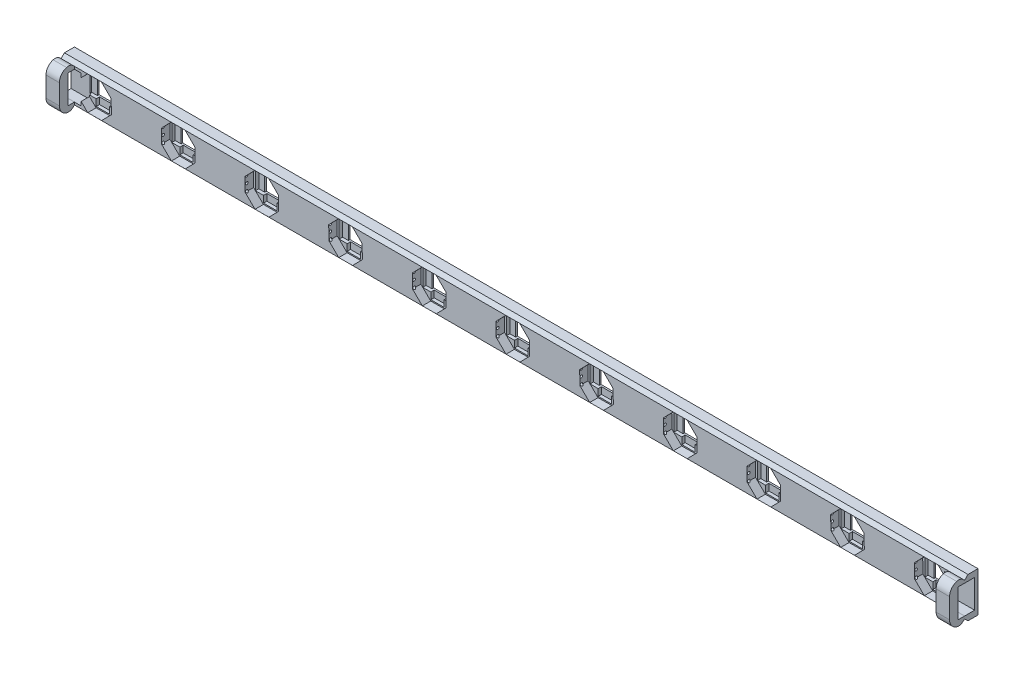
SolidWorks part; units mm, degrees
ref_plane "Front Plane" through (0, 0, 0) normal (0, 0, 1) x (1, 0, 0)
ref_plane "Top Plane" through (0, 0, 0) normal (0, 1, 0) x (1, 0, 0)
ref_plane "Right Plane" through (0, 0, 0) normal (1, 0, 0) x (0, 0, -1)
sketch "Sketch1" plane through (0, 0, 0) normal (0, 0, 1) x (1, 0, 0)
  line L1 (-279.6992, 7.2632) -> (-9.6992, 7.2632)
  line L2 (-279.6992, 7.2632) -> (-279.6992, -4.7368)
  line L3 (-279.6992, -4.7368) -> (-9.6992, -4.7368)
  line L4 (-9.6992, 7.2632) -> (-9.6992, -4.7368)
  dimension "D1" = 270
  dimension "D2" = 12
extrude "Boss-Extrude1" add sketch "Sketch1" along normal blind 4
sketch "Sketch3" plane through (0, 0, 4) normal (0, 0, 1) x (1, 0, 0)
  line L0 (-9.6992, -4.7368) -> (-9.6992, 7.2632) construction
  line L1 (-17.5892, -3.7205) -> (-14.6832, -0.7688)
  line L2 (-14.6832, -0.7688) -> (-14.7156, 3.3732)
  line L3 (-14.7156, 3.3732) -> (-17.6673, 6.2792)
  line L4 (-17.6673, 6.2792) -> (-21.8093, 6.2468)
  line L5 (-21.8093, 6.2468) -> (-24.7153, 3.2951)
  line L6 (-24.7153, 3.2951) -> (-24.6829, -0.8469)
  line L7 (-24.6829, -0.8469) -> (-21.7312, -3.7529)
  line L8 (-21.7312, -3.7529) -> (-17.5892, -3.7205)
  line L9 (-279.6992, -4.7368) -> (-9.6992, -4.7368) construction
  circle A0 centre (-19.6992, 1.2632) radius 5 construction
  dimension "D3" = 10
  dimension "D1" = 10
  dimension "D2" = 6
extrude "Cut-Extrude1" cut sketch "Sketch3" against normal blind 2.5
sketch "Sketch4" plane through (0, 0, 1.5) normal (0, 0, 1) x (1, 0, 0)
  line L1 (-22.3492, 3.9132) -> (-17.0492, 3.9132)
  line L2 (-22.3492, 3.9132) -> (-22.3492, -1.3868)
  line L3 (-22.3492, -1.3868) -> (-17.0492, -1.3868)
  line L4 (-17.0492, 3.9132) -> (-17.0492, -1.3868)
  line L13 (-9.6992, -4.7368) -> (-9.6992, 7.2632) construction
  line L14 (-279.6992, -4.7368) -> (-9.6992, -4.7368) construction
  dimension "D1" = 5.3
  dimension "D2" = 5.3
  dimension "D3" = 7.35
  dimension "D4" = 3.35
extrude "Cut-Extrude2" cut sketch "Sketch4" against normal through all
sketch "Sketch6" plane through (0, 0, 1.5) normal (0, 0, 1) x (1, 0, 0)
  line L0 (-22.3492, -1.3868) -> (-17.0492, -1.3868) construction
  line L1 (-21.6992, -1.3868) -> (-17.6992, -1.3868)
  line L2 (-21.6992, -1.3868) -> (-21.6992, -3.3868)
  line L3 (-21.6992, -3.3868) -> (-17.6992, -3.3868)
  line L4 (-17.6992, -1.3868) -> (-17.6992, -3.3868)
  line L7 (-9.6992, -4.7368) -> (-9.6992, 7.2632) construction
  line L8 (-279.6992, -4.7368) -> (-9.6992, -4.7368) construction
  dimension "D1" = 4
  dimension "D2" = 2
  dimension "D3" = 8
  dimension "D4" = 1.35
extrude "Cut-Extrude3" cut sketch "Sketch6" against normal blind 1
sketch "Sketch7" plane through (0, 0, 1.5) normal (0, 0, 1) x (1, 0, 0)
  line L0 (-17.0492, 3.9132) -> (-22.3492, 3.9132) construction
  line L1 (-21.6992, 3.9132) -> (-17.6992, 3.9132)
  line L2 (-21.6992, 3.9132) -> (-21.6992, 5.9132)
  line L3 (-21.6992, 5.9132) -> (-17.6992, 5.9132)
  line L4 (-17.6992, 3.9132) -> (-17.6992, 5.9132)
  line L6 (-9.6992, -4.7368) -> (-9.6992, 7.2632) construction
  dimension "D1" = 2
  dimension "D2" = 4
  dimension "D3" = 8
extrude "Cut-Extrude4" cut sketch "Sketch7" against normal blind 1
sketch "Sketch10" plane through (0, 0, 1.5) normal (0, 0, 1) x (1, 0, 0)
  line L1 (-17.0492, 3.9132) -> (-15.2992, 3.9132)
  line L2 (-17.0492, 3.9132) -> (-17.0492, -1.4203)
  line L3 (-17.0492, -1.4203) -> (-15.2992, -1.4203)
  line L4 (-15.2992, 3.9132) -> (-15.2992, -1.4203)
  line L5 (-22.3492, -1.3868) -> (-24.0992, -1.3868)
  line L6 (-22.3492, -1.3868) -> (-22.3492, 3.9132)
  line L7 (-22.3492, 3.9132) -> (-24.0992, 3.9132)
  line L8 (-24.0992, -1.3868) -> (-24.0992, 3.9132)
  dimension "D1" = 1.75
  dimension "D2" = 1.75
extrude "Cut-Extrude7" cut sketch "Sketch10" against normal blind 1
sketch "Sketch11" plane through (-9.6992, 0, 0) normal (1, 0, 0) x (0, 0, -1)
  line L0 (-4, -4.7368) -> (0, -4.7368) construction
  line L1 (-4, -4.7368) -> (-4, 7.2632) construction
  circle A0 centre (-3.5, 1.2632) radius 0.375
  dimension "D2" = 0.75
  dimension "D1" = 6
  dimension "D3" = 0.5
extrude "Cut-Extrude8" cut sketch "Sketch11" against normal through all both and the other way through all
sketch "Sketch12" plane through (-9.6992, 0, 0) normal (1, 0, 0) x (0, 0, -1)
  line L0 (-4, -4.7368) -> (-4, 7.2632) construction
  circle A0 centre (-3.5, -0.7368) radius 0.375
  circle A1 centre (-3.5, 1.2632) radius 0.375 construction
  dimension "D3" = 0.75
  dimension "D1" = 2
  dimension "D2" = 0.5
extrude "Cut-Extrude9" cut sketch "Sketch12" against normal through all both and the other way through all
sketch "Sketch13" plane through (-9.6992, 0, 0) normal (1, 0, 0) x (0, 0, -1)
  line L0 (-4, -4.7368) -> (-4, 7.2632) construction
  circle A0 centre (-3.5, 3.2632) radius 0.375
  circle A1 centre (-3.5, 1.2632) radius 0.375 construction
  dimension "D3" = 0.75
  dimension "D1" = 2
  dimension "D2" = 0.5
extrude "Cut-Extrude10" cut sketch "Sketch13" against normal through all both and the other way through all
sketch "Sketch14" plane through (0, 0, 4) normal (0, 0, 1) x (1, 0, 0)
  line L0 (-9.6992, -4.7368) -> (-9.6992, 7.2632) construction
  line L1 (-15.6992, 5.5132) -> (-9.6992, 5.5132)
  line L2 (-15.6992, 5.5132) -> (-15.6992, -2.9868)
  line L3 (-15.6992, -2.9868) -> (-9.6992, -2.9868)
  line L4 (-9.6992, 5.5132) -> (-9.6992, -2.9868)
  line L5 (-279.6992, -4.7368) -> (-9.6992, -4.7368) construction
  dimension "D1" = 8.5
  dimension "D2" = 1.75
  dimension "D3" = 6
extrude "Cut-Extrude11" cut sketch "Sketch14" against normal blind 3 and the other way through all
sketch "Sketch15" plane through (0, 0, 4) normal (0, 0, 1) x (1, 0, 0)
  line L0 (-279.6992, -4.7368) -> (-9.6992, -4.7368) construction
  line L1 (-9.6992, 7.2632) -> (-13.6992, 7.2632)
  line L2 (-9.6992, 7.2632) -> (-9.6992, -4.7368)
  line L3 (-9.6992, -4.7368) -> (-13.6992, -4.7368)
  line L4 (-13.6992, 7.2632) -> (-13.6992, -4.7368)
  dimension "D1" = 4
extrude "Boss-Extrude2" add sketch "Sketch15" along normal blind 4.5
sketch "Sketch16" plane through (-9.6992, 0, 0) normal (1, 0, 0) x (0, 0, -1)
  line L1 (-4, 5.5132) -> (-6, 5.5132)
  line L2 (-4, 5.5132) -> (-4, -2.9871)
  line L3 (-4, -2.9871) -> (-6, -2.9871)
  line L4 (-6, 5.5132) -> (-6, -2.9871)
  dimension "D1" = 2
extrude "Cut-Extrude12" cut sketch "Sketch16" against normal blind 4.5
fillet "Fillet1" radius 3 1 edges at (-11.6992, 7.2632, 8.5)
fillet "Fillet2" radius 3 1 edges at (-11.6992, -4.7368, 8.5)
sketch "Sketch17" plane through (0, 0, 4) normal (0, 0, 1) x (1, 0, 0)
  line L0 (-279.6992, 7.2632) -> (-279.6992, -4.7368) construction
  line L1 (-279.6992, 5.5132) -> (-273.6992, 5.5132)
  line L2 (-279.6992, 5.5132) -> (-279.6992, -2.9868)
  line L3 (-279.6992, -2.9868) -> (-273.6992, -2.9868)
  line L4 (-273.6992, 5.5132) -> (-273.6992, -2.9868)
  line L5 (-279.6992, -4.7368) -> (-13.6992, -4.7368) construction
  dimension "D1" = 6
  dimension "D2" = 8.5
  dimension "D3" = 1.75
extrude "Cut-Extrude13" cut sketch "Sketch17" against normal blind 3
sketch "Sketch18" plane through (0, 0, 4) normal (0, 0, 1) x (1, 0, 0)
  line L0 (-279.6992, -4.7368) -> (-13.6992, -4.7368) construction
  line L1 (-279.6992, 7.2632) -> (-275.6992, 7.2632)
  line L2 (-279.6992, 7.2632) -> (-279.6992, -4.7368)
  line L3 (-279.6992, -4.7368) -> (-275.6992, -4.7368)
  line L4 (-275.6992, 7.2632) -> (-275.6992, -4.7368)
  dimension "D1" = 4
extrude "Boss-Extrude3" add sketch "Sketch18" along normal blind 4.5
sketch "Sketch19" plane through (-279.6992, 0, 0) normal (-1, 0, 0) x (0, 0, 1)
  line L1 (4, 5.5132) -> (6, 5.5132)
  line L2 (4, 5.5132) -> (4, -2.9862)
  line L3 (4, -2.9862) -> (6, -2.9862)
  line L4 (6, 5.5132) -> (6, -2.9862)
  dimension "D1" = 2
extrude "Cut-Extrude14" cut sketch "Sketch19" against normal blind 4.5
fillet "Fillet3" radius 3 1 edges at (-277.6992, 7.2632, 8.5)
fillet "Fillet4" radius 3 1 edges at (-277.6992, -4.7368, 8.5)
chamfer "Chamfer1" distance 1 angle 45 1 edges at (-144.6992, 7.2632, 4)
chamfer "Chamfer2" distance 1 angle 45 1 edges at (-144.6992, -4.7368, 4)
sketch "Sketch30" plane through (-275.6992, 0, 0) normal (1, 0, 0) x (0, 0, -1)
  line L0 (-3, -4.7368) -> (-4, -3.7368)
  line L1 (-4, -3.7368) -> (-4, -4.7368)
  line L2 (-5.5, -4.7368) -> (-3, -4.7368) construction
  line L3 (-4, -4.7368) -> (-3, -4.7368)
extrude "Cut-Extrude15" cut sketch "Sketch30" along normal through all both and the other way through all
sketch "Sketch31" plane through (-275.6992, 0, 0) normal (1, 0, 0) x (0, 0, -1)
  line L0 (-4, 6.2632) -> (-3, 7.2632)
  line L1 (-3, 7.2632) -> (-4, 7.2632)
  line L2 (-5.5, 7.2632) -> (-3, 7.2632) construction
  line L3 (-4, 7.2632) -> (-4, 6.2632)
extrude "Cut-Extrude16" cut sketch "Sketch31" against normal through all both and the other way through all
chamfer "Chamfer3" distance 1 angle 45 1 edges at (-277.6992, 7.2632, 4)
chamfer "Chamfer4" distance 1 angle 45 1 edges at (-11.6992, 7.2632, 4)
chamfer "Chamfer5" distance 1 angle 45 1 edges at (-11.6992, -4.7368, 4)
chamfer "Chamfer6" distance 1 angle 45 1 edges at (-277.6992, -4.7368, 4)
fillet "Fillet5" radius 2 1 edges at (-11.6992, 7.2632, 5)
fillet "Fillet6" radius 2 1 edges at (-11.6992, -4.7368, 5)
fillet "Fillet7" radius 2 1 edges at (-277.6992, -4.7368, 5)
fillet "Fillet8" radius 2 1 edges at (-277.6992, 7.2632, 5)
pattern_linear "LPattern1" count 11 spacing 25 along (-1, 0, 0) of "Cut-Extrude1", "Cut-Extrude2", "Cut-Extrude3", "Cut-Extrude4", "Cut-Extrude7"
